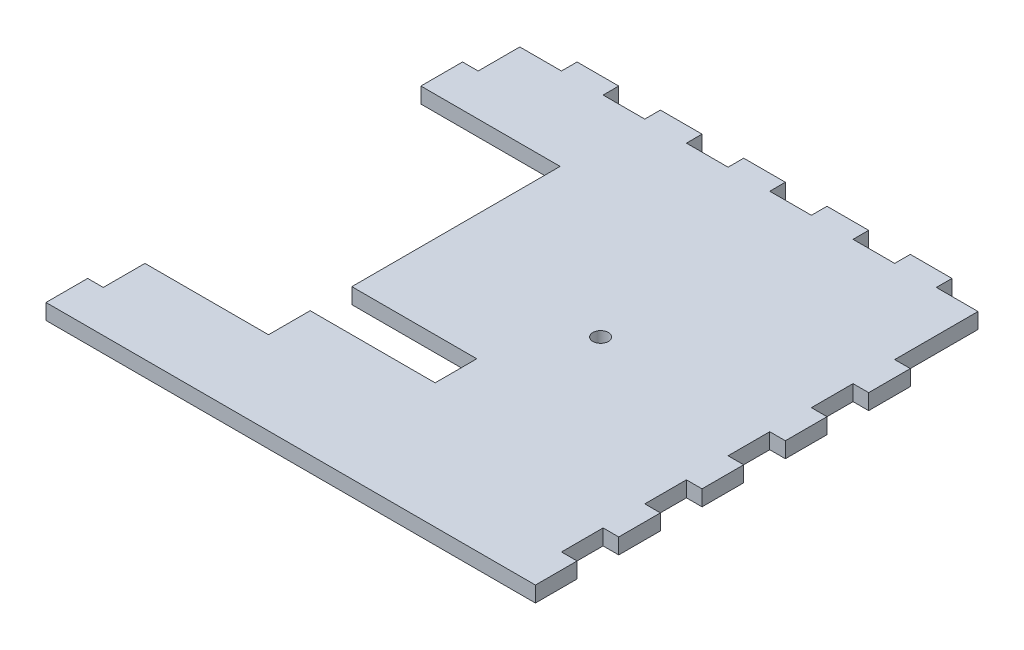
SolidWorks part; units mm, degrees
ref_plane "Front Plane" through (0, 0, 0) normal (0, 0, 1) x (1, 0, 0)
ref_plane "Top Plane" through (0, 0, 0) normal (0, 1, 0) x (1, 0, 0)
ref_plane "Right Plane" through (0, 0, 0) normal (1, 0, 0) x (0, 0, -1)
sketch "Sketch1" plane through (0, 0, 0) normal (0, 1, 0) x (1, 0, 0)
  line L1 (-139.7, -139.7) -> (139.7, -139.7)
  line L2 (-139.7, -139.7) -> (-139.7, 139.7)
  line L3 (-139.7, 139.7) -> (139.7, 139.7)
  line L4 (139.7, -139.7) -> (139.7, 139.7)
  line L5 (-139.7, -139.7) -> (139.7, 139.7) construction
  line L6 (-139.7, 139.7) -> (139.7, -139.7) construction
  point P0 (0, 0)
  dimension "D1" = 279.4
  dimension "D2" = 279.4
extrude "Boss-Extrude1" add sketch "Sketch1" along normal blind 9.525
sketch "Sketch2" plane through (139.7, 0, 0) normal (1, 0, 0) x (0, 0, -1)
  line L0 (-139.7, 9.525) -> (139.7, 9.525) construction
  line L1 (-139.7, 0) -> (-114.3, 0)
  line L2 (-139.7, 0) -> (-139.7, 9.525)
  line L3 (-139.7, 9.525) -> (-114.3, 9.525)
  line L4 (-114.3, 0) -> (-114.3, 9.525)
  dimension "D1" = 25.4
extrude "Boss-Extrude2" add sketch "Sketch2" along normal blind 9.525
pattern_linear "LPattern1" count 5 spacing 50.8 along (0, 0, -1) of "Boss-Extrude2"
mirror "Mirror1" about plane through (0, 0, 0) normal (1, 0, 0) of "LPattern1"
sketch "Sketch3" plane through (0, 0, -139.7) normal (0, 0, -1) x (-1, 0, 0)
  line L0 (-139.7, 9.525) -> (139.7, 9.525) construction
  line L1 (-114.3, 9.525) -> (-88.9, 9.525)
  line L2 (-114.3, 9.525) -> (-114.3, 0)
  line L3 (-114.3, 0) -> (-88.9, 0)
  line L4 (-88.9, 9.525) -> (-88.9, 0)
  line L5 (-139.7, 0) -> (139.7, 0) construction
  line L7 (-149.225, 0) -> (-149.225, 9.525) construction
  dimension "D1" = 34.925
  dimension "D2" = 25.4
extrude "Boss-Extrude3" add sketch "Sketch3" along normal blind 9.525
pattern_linear "LPattern2" count 5 spacing 50.8 along (-1, 0, 0) of "Boss-Extrude3"
sketch "Sketch6" plane through (0, 9.525, 0) normal (0, 1, 0) x (1, 0, 0)
  line L0 (38.1, 139.7) -> (12.7, 139.7) construction
  line L1 (139.7, -12.7) -> (139.7, 12.7) construction
  circle A0 centre (38.1, 11.176) radius 4.7625
  dimension "D1" = 128.524
  dimension "D3" = 9.525
  dimension "D2" = 101.6
extrude "Cut-Extrude1" cut sketch "Sketch6" against normal through all
sketch "Sketch8" plane through (0, 9.525, 0) normal (0, 1, 0) x (1, 0, 0)
  line L1 (-149.225, 88.9) -> (-64.3339, 88.9)
  line L2 (-149.225, 88.9) -> (-149.225, -88.9)
  line L3 (-149.225, -88.9) -> (-64.3339, -88.9)
  line L4 (-64.3339, 88.9) -> (-64.3339, -88.9)
  dimension "D1" = 177.8
extrude "Cut-Extrude3" cut sketch "Sketch8" against normal through all
sketch "Sketch7" plane through (0, 9.525, 0) normal (0, 1, 0) x (1, 0, 0)
  line L2 (-114.3, 139.7) -> (-139.7, 139.7) construction
  line L3 (-139.7, 139.7) -> (-139.7, 88.9) construction
  circle A0 centre (-101.6, 65.278) radius 5.08
  circle A1 centre (-101.6, 27.686) radius 5.08
  dimension "D1" = 10.16
  dimension "D2" = 10.16
  dimension "D3" = 38.1
  dimension "D5" = 37.592
  dimension "D6" = 74.422
sketch "Sketch9" plane through (-139.7, 0, 0) normal (-1, 0, 0) x (0, 0, 1)
  line L0 (153.67, 0) -> (-153.67, 0) construction
  line L1 (-88.9, 9.525) -> (-114.3, 9.525)
  line L2 (-88.9, 9.525) -> (-88.9, 0)
  line L3 (-88.9, 0) -> (-114.3, 0)
  line L4 (-114.3, 9.525) -> (-114.3, 0)
  dimension "D1" = 25.4
extrude "Boss-Extrude4" add sketch "Sketch9" along normal blind 9.525
sketch "Sketch11" plane through (-64.3339, 0, 0) normal (-1, 0, 0) x (0, 0, 1)
  line L6 (88.9, 0) -> (-88.9, 0) construction
  line L7 (63.5, 0) -> (38.1, 0)
  line L8 (63.5, 0) -> (63.5, 9.525)
  line L9 (63.5, 9.525) -> (38.1, 9.525)
  line L10 (38.1, 0) -> (38.1, 9.525)
  line L11 (88.9, 9.525) -> (-88.9, 9.525) construction
  line L12 (88.9, 0) -> (88.9, 9.525) construction
  dimension "D1" = 25.4
  dimension "D2" = 25.4
extrude "Cut-Extrude4" cut sketch "Sketch11" against normal blind 76.2
